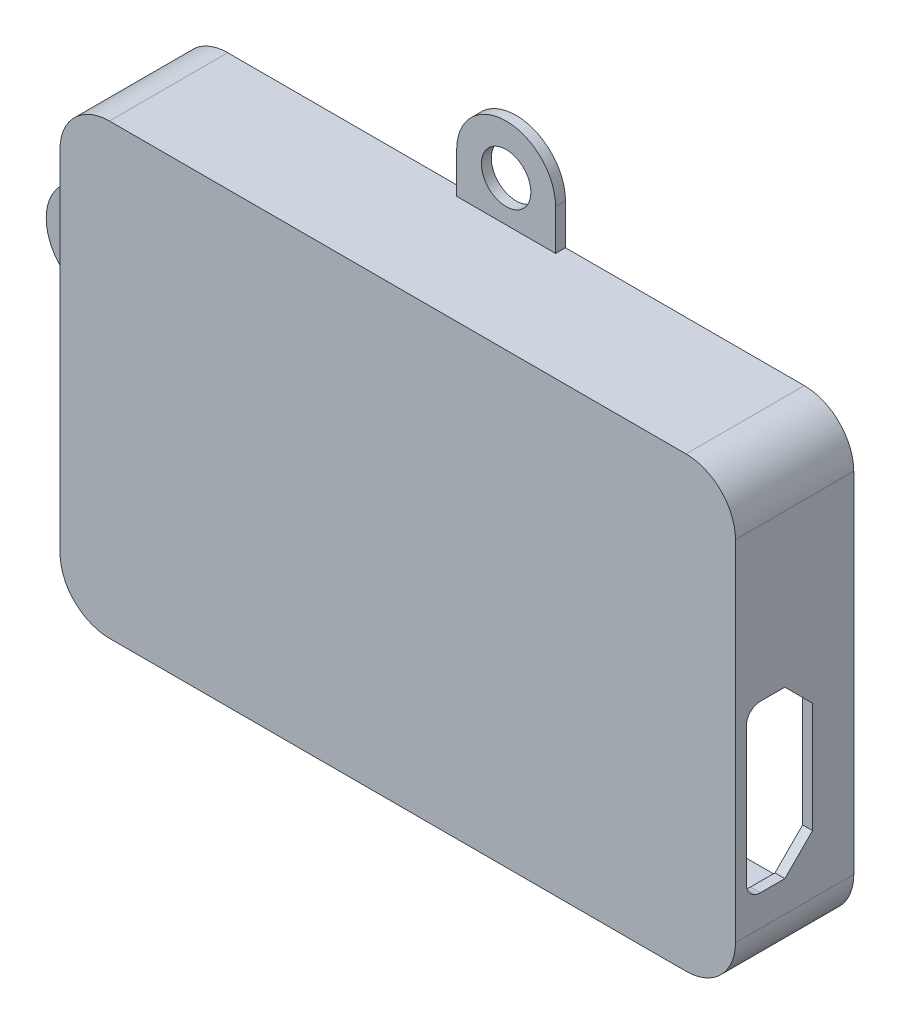
SolidWorks part; units mm, degrees
ref_plane "Front Plane" through (0, 0, 0) normal (0, 0, 1) x (1, 0, 0)
ref_plane "Top Plane" through (0, 0, 0) normal (0, 1, 0) x (1, 0, 0)
ref_plane "Right Plane" through (0, 0, 0) normal (1, 0, 0) x (0, 0, -1)
sketch "Sketch1" plane through (0, 0, 0) normal (0, 0, 1) x (1, 0, 0)
  line L1 (-14.575, -11.325) -> (14.575, -11.325)
  line L2 (-17.075, -8.825) -> (-17.075, 8.825)
  line L3 (-14.575, 11.325) -> (14.575, 11.325)
  line L4 (17.075, -8.825) -> (17.075, 8.825)
  line L5 (-17.075, -11.325) -> (17.075, 11.325) construction
  line L6 (-17.075, 11.325) -> (17.075, -11.325) construction
  line L8 (-16.575, 10.825) -> (-17.075, 10.825) construction
  line L9 (14.575, -10.825) -> (-14.575, -10.825)
  line L10 (16.575, -8.825) -> (16.575, 8.825)
  line L11 (14.575, 10.825) -> (-14.575, 10.825)
  line L12 (-16.575, -8.825) -> (-16.575, 8.825)
  line L13 (16.575, -10.825) -> (-16.575, 10.825) construction
  line L14 (16.575, 10.825) -> (-16.575, -10.825) construction
  line L15 (-16.575, 10.825) -> (-16.575, 11.325) construction
  line L16 (-16.375, 9.825) -> (-16.375, -9.825) construction
  line L17 (16.375, 9.825) -> (-16.375, 9.825) construction
  line L18 (-2.5, 13.375) -> (-2.5, 11.325)
  line L19 (2.5, 13.375) -> (2.5, 11.325)
  line L20 (-2.5, -13.375) -> (-2.5, -11.325)
  line L21 (2.5, -13.375) -> (2.5, -11.325)
  line L22 (-20.75, 2.5) -> (-17.075, 2.5)
  line L23 (-20.75, -2.5) -> (-17.075, -2.5)
  arc A0 (-14.575, -10.825) -> (-16.575, -8.825) centre (-14.575, -8.825) cw
  arc A1 (-2.4744, -13.0179) -> (2.4744, -13.0179) centre (0, -13.375) ccw construction
  arc A2 (14.575, -10.825) -> (16.575, -8.825) centre (14.575, -8.825) ccw
  arc A3 (16.575, 8.825) -> (14.575, 10.825) centre (14.575, 8.825) ccw
  arc A4 (-20.3929, 2.4744) -> (-20.3929, -2.4744) centre (-20.75, 0) ccw construction
  arc A5 (-14.575, 10.825) -> (-16.575, 8.825) centre (-14.575, 8.825) ccw
  arc A6 (-14.575, -11.325) -> (-17.075, -8.825) centre (-14.575, -8.825) cw
  arc A7 (14.575, -11.325) -> (17.075, -8.825) centre (14.575, -8.825) ccw
  arc A8 (2.4744, 13.0179) -> (-2.4744, 13.0179) centre (0, 13.375) ccw construction
  circle A9 centre (-20.75, 0) radius 1.25
  arc A10 (-2.4744, -13.0179) -> (2.4744, -13.0179) centre (0, -13.375) ccw
  circle A11 centre (0, 13.375) radius 1.25
  circle A12 centre (0, -13.375) radius 1.25
  arc A13 (-20.3929, 2.4744) -> (-20.3929, -2.4744) centre (-20.75, 0) ccw
  arc A14 (14.575, 11.325) -> (17.075, 8.825) centre (14.575, 8.825) cw
  arc A15 (-17.075, 8.825) -> (-14.575, 11.325) centre (-14.575, 8.825) cw
  arc A17 (2.4744, 13.0179) -> (-2.4744, 13.0179) centre (0, 13.375) ccw
  point P0 (0, 0)
  point P31 (0, 0)
  dimension "D4" = 2.5
  dimension "D5" = 2
  dimension "D6" = 2.5
  dimension "D1" = 0.5
  dimension "D2" = 0.2
  dimension "D3" = 1
extrude "Boss-Extrude1" add sketch "Sketch1" along normal offset from surface (5.48 mm away) 0.5 contours A13 L2 | L1 L4 L3 L2 L9 L12 L11 L10 | A17 L3 | A10 L1 region at (-16.053, -10.303, 0) region at (0, -11.3926, 0) region at (-18.9125, -2.4205, 0) region at (-2.4324, 12.35, 0) offset beyond the face yes
sketch "Sketch2" plane through (0, 0, 5.48) normal (0, 0, 1) x (1, 0, 0)
  line L0 (-2.5, 11.325) -> (2.5, 11.325)
  line L1 (-17.075, 2.5) -> (-17.075, -2.5)
  line L2 (-2.5, -11.325) -> (2.5, -11.325)
  line L13 (-17.075, 2.5) -> (-20.75, 2.5)
  line L14 (-20.75, -2.5) -> (-17.075, -2.5)
  line L15 (-17.075, -2.5) -> (-17.075, -8.825)
  line L16 (-14.575, -11.325) -> (-2.5, -11.325)
  line L17 (-2.5, -11.325) -> (-2.5, -13.375)
  line L18 (2.5, -13.375) -> (2.5, -11.325)
  line L19 (2.5, -11.325) -> (14.575, -11.325)
  line L20 (17.075, -8.825) -> (17.075, 8.825)
  line L21 (14.575, 11.325) -> (2.5, 11.325)
  line L22 (2.5, 11.325) -> (2.5, 13.375)
  line L23 (-2.5, 13.375) -> (-2.5, 11.325)
  line L24 (-2.5, 11.325) -> (-14.575, 11.325)
  line L25 (-17.075, 8.825) -> (-17.075, 2.5)
  line L26 (-17.075, 2.5) -> (-20.75, 2.5)
  line L27 (-20.75, -2.5) -> (-17.075, -2.5)
  line L28 (-17.075, -2.5) -> (-17.075, -8.825)
  line L29 (-14.575, -11.325) -> (-2.5, -11.325)
  line L30 (-2.5, -11.325) -> (-2.5, -13.375)
  line L31 (2.5, -13.375) -> (2.5, -11.325)
  line L32 (2.5, -11.325) -> (14.575, -11.325)
  line L33 (17.075, -8.825) -> (17.075, 8.825)
  line L34 (14.575, 11.325) -> (2.5, 11.325)
  line L35 (2.5, 11.325) -> (2.5, 13.375)
  line L36 (-2.5, 13.375) -> (-2.5, 11.325)
  line L37 (-2.5, 11.325) -> (-14.575, 11.325)
  line L38 (-17.075, 8.825) -> (-17.075, 2.5)
  arc A7 (-20.75, 2.5) -> (-20.75, -2.5) centre (-20.75, 0) ccw
  arc A8 (-17.075, -8.825) -> (-14.575, -11.325) centre (-14.575, -8.825) ccw
  arc A9 (-2.5, -13.375) -> (2.5, -13.375) centre (0, -13.375) ccw
  arc A10 (14.575, -11.325) -> (17.075, -8.825) centre (14.575, -8.825) ccw
  arc A11 (17.075, 8.825) -> (14.575, 11.325) centre (14.575, 8.825) ccw
  arc A12 (2.5, 13.375) -> (-2.5, 13.375) centre (0, 13.375) ccw
  arc A13 (-14.575, 11.325) -> (-17.075, 8.825) centre (-14.575, 8.825) ccw
  arc A14 (-20.75, 2.5) -> (-20.75, -2.5) centre (-20.75, 0) ccw
  arc A15 (-17.075, -8.825) -> (-14.575, -11.325) centre (-14.575, -8.825) ccw
  arc A16 (-2.5, -13.375) -> (2.5, -13.375) centre (0, -13.375) ccw
  arc A17 (14.575, -11.325) -> (17.075, -8.825) centre (14.575, -8.825) ccw
  arc A18 (17.075, 8.825) -> (14.575, 11.325) centre (14.575, 8.825) ccw
  arc A19 (2.5, 13.375) -> (-2.5, 13.375) centre (0, 13.375) ccw
  arc A20 (-14.575, 11.325) -> (-17.075, 8.825) centre (-14.575, 8.825) ccw
  arc M18 (-20.75, 2.5) -> (-20.75, -2.5) centre (-20.75, 0) ccw
  arc M23 (-2.5, -13.375) -> (2.5, -13.375) centre (0, -13.375) ccw
  arc M29 (2.5, 13.375) -> (-2.5, 13.375) centre (0, 13.375) ccw
  circle M57 centre (0, 13.375) radius 1.25
  circle M62 centre (-20.75, 0) radius 1.25
  line M63 (-17.075, 2.5) -> (-20.75, 2.5)
  line M64 (-20.75, -2.5) -> (-17.075, -2.5)
  line M68 (-2.5, -11.325) -> (-2.5, -13.375)
  line M69 (2.5, -13.375) -> (2.5, -11.325)
  line M74 (2.5, 11.325) -> (2.5, 13.375)
  line M75 (-2.5, 13.375) -> (-2.5, 11.325)
  circle M79 centre (0, -13.375) radius 1.25
  dimension "D1" = 0
extrude "Cut-Extrude1" cut sketch "Sketch2" against normal offset from surface (4.98 mm away) 0.5 contours L0 M75 M74 M29 M57 | L1 M63 M18 M64 M62 | L2 M68 M23 M69 M79 region at (-2.4324, 12.35, 5.48) region at (-17.1545, 0, 5.48) region at (2.4324, -12.35, 5.48) up to face at (-3.9075, 0, 0)
sketch "Sketch3" plane through (17.075, 0, 0) normal (1, 0, 0) x (0, 0, -1)
  line L0 (-3.98, -7.065) -> (-4.18, -7.065) construction
  line L1 (-5.425, -7.265) -> (-2.085, -7.265)
  line L2 (-5.425, -7.265) -> (-5.425, 1.115)
  line L3 (-5.425, 1.115) -> (-2.085, 1.115)
  line L4 (-2.085, -7.265) -> (-2.085, 1.115)
  line L5 (-5.225, -6.075) -> (-5.425, -6.075) construction
  line L6 (-4.18, -7.065) -> (-4.18, -7.265) construction
  line L7 (-4.18, 0.915) -> (-4.18, 1.115) construction
  line L8 (-2.285, -5.375) -> (-2.085, -5.375) construction
  dimension "D1" = 0.2
extrude "Cut-Extrude2" cut sketch "Sketch3" against normal up to next
chamfer "Chamfer1" distance 1.4 angle 45 2 edges at (16.825, 1.115, 2.085) (16.825, -7.265, 2.085)
fillet "Fillet1" radius 0.7 2 edges at (16.825, 1.115, 5.425) (16.825, -7.265, 5.425)
sketch "Sketch4" plane through (0, 0, 5.48) normal (0, 0, 1) x (1, 0, 0)
  line L4 (-17.075, 8.825) -> (-17.075, -8.825)
  line L5 (-14.575, -11.325) -> (14.575, -11.325)
  line L6 (17.075, -8.825) -> (17.075, 8.825)
  line L7 (14.575, 11.325) -> (-14.575, 11.325)
  line L8 (-17.075, 8.825) -> (-17.075, -8.825)
  line L9 (-14.575, -11.325) -> (14.575, -11.325)
  line L10 (17.075, -8.825) -> (17.075, 8.825)
  line L11 (14.575, 11.325) -> (-14.575, 11.325)
  arc A4 (-17.075, -8.825) -> (-14.575, -11.325) centre (-14.575, -8.825) ccw
  arc A5 (14.575, -11.325) -> (17.075, -8.825) centre (14.575, -8.825) ccw
  arc A6 (17.075, 8.825) -> (14.575, 11.325) centre (14.575, 8.825) ccw
  arc A7 (-14.575, 11.325) -> (-17.075, 8.825) centre (-14.575, 8.825) ccw
  arc A8 (-17.075, -8.825) -> (-14.575, -11.325) centre (-14.575, -8.825) ccw
  arc A9 (14.575, -11.325) -> (17.075, -8.825) centre (14.575, -8.825) ccw
  arc A10 (17.075, 8.825) -> (14.575, 11.325) centre (14.575, 8.825) ccw
  arc A11 (-14.575, 11.325) -> (-17.075, 8.825) centre (-14.575, 8.825) ccw
  dimension "D1" = 0
extrude "Boss-Extrude2" add sketch "Sketch4" along normal blind 0.5
sketch "Sketch5" [suppressed] plane through (0, 0, 0.5) normal (0, 0, 1) x (1, 0, 0)
  line L0 (2.5, -13.375) -> (2.5, -11.325) construction
  line L1 (2.5, -11.325) -> (-2.5, -11.325) construction
  line L2 (-2.5, -11.325) -> (-2.5, -13.375) construction
  line L3 (-2.5, 13.375) -> (-2.5, 11.325) construction
  line L4 (-2.5, 11.325) -> (2.5, 11.325) construction
  line L5 (2.5, 11.325) -> (2.5, 13.375) construction
  line L6 (-20.75, -2.5) -> (-17.075, -2.5) construction
  line L7 (-17.075, -2.5) -> (-17.075, 2.5) construction
  line L8 (-17.075, 2.5) -> (-20.75, 2.5) construction
  line L9 (2.5, -13.375) -> (2.5, -11.325)
  line L10 (2.5, -11.325) -> (-2.5, -11.325)
  line L11 (-2.5, -11.325) -> (-2.5, -13.375)
  line L12 (-2.5, 13.375) -> (-2.5, 11.325)
  line L13 (-2.5, 11.325) -> (2.5, 11.325)
  line L14 (2.5, 11.325) -> (2.5, 13.375)
  line L15 (-20.75, -2.5) -> (-17.075, -2.5)
  line L16 (-17.075, -2.5) -> (-17.075, 2.5)
  line L17 (-17.075, 2.5) -> (-20.75, 2.5)
  line L18 (-2.5, 11.825) -> (2.5, 11.825)
  line L19 (-20.75, 2) -> (-20.75, 2.5) construction
  line L20 (0, 11.825) -> (0, 11.325) construction
  line L21 (-17.075, 0) -> (17.075, 0) construction
  line L22 (17.075, -8.825) -> (17.075, 8.825) construction
  line L23 (-2.5, -11.825) -> (2.5, -11.825)
  arc A0 (-2.5, -13.375) -> (2.5, -13.375) centre (0, -13.375) ccw construction
  arc A1 (2.5, 13.375) -> (-2.5, 13.375) centre (0, 13.375) ccw construction
  arc A2 (-20.75, 2.5) -> (-20.75, -2.5) centre (-20.75, 0) ccw construction
  arc A3 (-2.5, -13.375) -> (2.5, -13.375) centre (0, -13.375) ccw
  arc A4 (2.5, 13.375) -> (-2.5, 13.375) centre (0, 13.375) ccw
  arc A5 (-20.75, 2.5) -> (-20.75, -2.5) centre (-20.75, 0) ccw
  circle A6 centre (-20.75, 0) radius 2
  circle A7 centre (-20.75, 0) radius 2.5
  circle A8 centre (0, 13.375) radius 2.5
  circle A9 centre (0, -13.375) radius 2.5
  circle A10 centre (0, 13.375) radius 2
  circle A11 centre (0, -13.375) radius 2
  arc M9 (-20.75, 2.5) -> (-20.75, -2.5) centre (-20.75, 0) ccw
  dimension "D1" = 0.5
extrude "Boss-Extrude3" [suppressed] add sketch "Sketch5" along normal up to surface (7.48 mm away) contours A10 L18 A8 A4 | A7 A6 M9 | A11 L23 A9 A3 up to face at (0, 0, 5.98)
sketch "Sketch6" plane through (0, 0, 5.48) normal (0, 0, -1) x (-1, 0, 0)
  line L1 (-14.575, -10.825) -> (-16.575, -10.825)
  line L2 (-14.575, -10.825) -> (-14.575, -9.325)
  line L3 (-14.575, -9.325) -> (-16.575, -9.325)
  line L4 (16.575, -8.825) -> (16.575, 8.825)
  line L5 (14.575, 10.825) -> (-14.575, 10.825)
  line L6 (-16.575, 8.825) -> (-16.575, -8.825)
  line L7 (-14.575, -10.825) -> (14.575, -10.825)
  line L8 (16.575, -8.825) -> (16.575, 8.825)
  line L9 (14.575, 10.825) -> (-14.575, 10.825)
  line L10 (-16.575, 8.825) -> (-16.575, -8.825)
  line L11 (-14.575, -10.825) -> (14.575, -10.825)
  line L12 (-16.575, -10.825) -> (-16.575, -9.325)
  line L13 (-16.575, 1.915) -> (-14.575, 1.915)
  line L14 (-16.575, 1.915) -> (-16.575, 3.415)
  line L15 (-16.575, 3.415) -> (-14.575, 3.415)
  line L16 (-14.575, 1.915) -> (-14.575, 3.415)
  line L17 (-14.575, 10.825) -> (-16.575, 10.825)
  line L18 (-14.575, 10.825) -> (-14.575, 9.325)
  line L19 (-14.575, 9.325) -> (-16.575, 9.325)
  line L20 (-16.575, 10.825) -> (-16.575, 9.325)
  line L21 (16.575, 10.825) -> (14.575, 10.825)
  line L22 (16.575, 10.825) -> (16.575, 9.325)
  line L23 (16.575, 9.325) -> (14.575, 9.325)
  line L24 (14.575, 10.825) -> (14.575, 9.325)
  line L25 (10.575, -10.825) -> (7.575, -10.825)
  line L26 (10.575, -10.825) -> (10.575, -9.325)
  line L27 (10.575, -9.325) -> (7.575, -9.325)
  line L28 (7.575, -10.825) -> (7.575, -9.325)
  arc A4 (14.575, -10.825) -> (16.575, -8.825) centre (14.575, -8.825) ccw
  arc A5 (16.575, 8.825) -> (14.575, 10.825) centre (14.575, 8.825) ccw
  arc A6 (-14.575, 10.825) -> (-16.575, 8.825) centre (-14.575, 8.825) ccw
  arc A7 (-16.575, -8.825) -> (-14.575, -10.825) centre (-14.575, -8.825) ccw
  arc A8 (14.575, -10.825) -> (16.575, -8.825) centre (14.575, -8.825) ccw
  arc A9 (16.575, 8.825) -> (14.575, 10.825) centre (14.575, 8.825) ccw
  arc A10 (-14.575, 10.825) -> (-16.575, 8.825) centre (-14.575, 8.825) ccw
  arc A11 (-16.575, -8.825) -> (-14.575, -10.825) centre (-14.575, -8.825) ccw
  arc M24 (16.575, 8.825) -> (14.575, 10.825) centre (14.575, 8.825) ccw
  arc M26 (-14.575, 10.825) -> (-16.575, 8.825) centre (-14.575, 8.825) ccw
  arc M28 (-16.575, -8.825) -> (-14.575, -10.825) centre (-14.575, -8.825) ccw
  dimension "D2" = 1.5
  dimension "D3" = 1.5
  dimension "D5" = 3
  dimension "D6" = 6
  dimension "D1" = 0
extrude "Boss-Extrude4" add sketch "Sketch6" along normal offset from surface (2.98 mm away) 2.5 contours L28 L11 L26 L27 | L2 L3 M28 | L13 L16 L15 L10 | L19 L18 M26 | L24 L23 M24 region at (15.3591, -9.9498, 5.48) region at (-9.075, -10.075, 5.48) region at (15.575, 2.665, 5.48) region at (-15.3591, 9.9498, 5.48) region at (15.3591, 9.9498, 5.48) up to face at (-3.9075, 0, 0)
